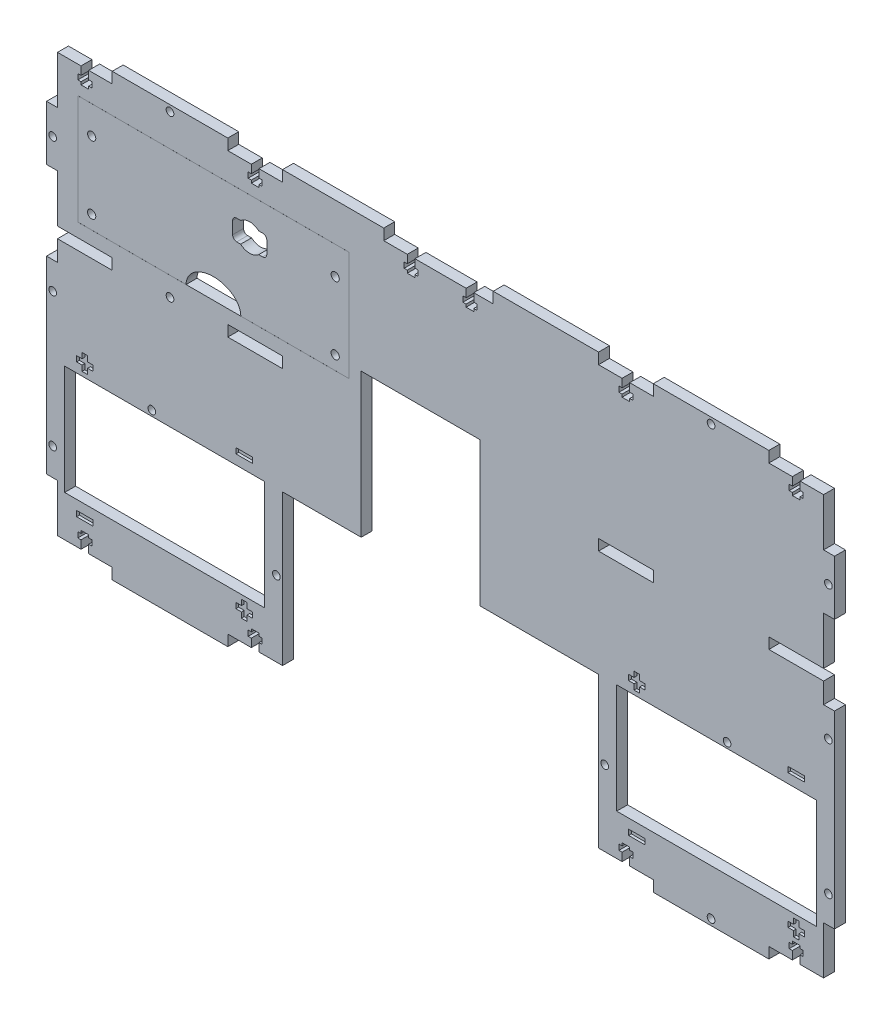
SolidWorks part; units mm, degrees
ref_plane "Спереди" through (0, 0, 0) normal (0, 0, 1) x (1, 0, 0)
ref_plane "Сверху" through (0, 0, 0) normal (0, 1, 0) x (1, 0, 0)
ref_plane "Справа" through (0, 0, 0) normal (1, 0, 0) x (0, 0, -1)
sketch "Эскиз1" plane through (0, 0, 0) normal (0, 0, 1) x (1, 0, 0)
  line L1 (-144, -80.5) -> (144, -80.5)
  line L2 (-144, -80.5) -> (-144, 80.5)
  line L3 (-144, 80.5) -> (144, 80.5)
  line L4 (144, -80.5) -> (144, 80.5)
  line L5 (-144, -80.5) -> (144, 80.5) construction
  line L6 (-144, 80.5) -> (144, -80.5) construction
  line L14 (144, 59) -> (144, 80.5) construction
  line L15 (144, 80.5) -> (140, 80.5) construction
  line L16 (140, 80.5) -> (140, 59) construction
  line L17 (140, 59) -> (144, 59) construction
  line L18 (140, 80.5) -> (120, 80.5) construction
  line L19 (120, 80.5) -> (120, 76.5) construction
  line L20 (120, 76.5) -> (140, 76.5) construction
  line L21 (140, 76.5) -> (140, 80.5) construction
  line L22 (77.75, 80.5) -> (57.75, 80.5) construction
  line L23 (57.75, 80.5) -> (57.75, 76.5) construction
  line L24 (57.75, 76.5) -> (77.75, 76.5) construction
  line L25 (77.75, 76.5) -> (77.75, 80.5) construction
  line L26 (19.25, 80.5) -> (-20.75, 80.5) construction
  line L27 (-20.75, 80.5) -> (-20.75, 76.5) construction
  line L28 (-20.75, 76.5) -> (19.25, 76.5) construction
  line L29 (19.25, 76.5) -> (19.25, 80.5) construction
  line L30 (-57.75, 80.5) -> (-77.75, 80.5) construction
  line L31 (-77.75, 80.5) -> (-77.75, 76.5) construction
  line L32 (-77.75, 76.5) -> (-57.75, 76.5) construction
  line L33 (-57.75, 76.5) -> (-57.75, 80.5) construction
  line L34 (-120, 80.5) -> (-140, 80.5) construction
  line L35 (-140, 80.5) -> (-140, 76.5) construction
  line L36 (-140, 76.5) -> (-120, 76.5) construction
  line L37 (-120, 76.5) -> (-120, 80.5) construction
  line L38 (-140, 59) -> (-140, 80.5) construction
  line L39 (-140, 80.5) -> (-144, 80.5) construction
  line L40 (-144, 80.5) -> (-144, 59) construction
  line L41 (-144, 59) -> (-140, 59) construction
  line L42 (-77.75, 17.5) -> (-57.75, 17.5) construction
  line L43 (-57.75, 17.5) -> (-57.75, 21.5) construction
  line L44 (-57.75, 21.5) -> (-77.75, 21.5) construction
  line L45 (-77.75, 21.5) -> (-77.75, 17.5) construction
  line L46 (-140, 17.5) -> (-120, 17.5) construction
  line L47 (-120, 17.5) -> (-120, 21.5) construction
  line L48 (-120, 21.5) -> (-140, 21.5) construction
  line L49 (-140, 21.5) -> (-140, 17.5) construction
  line L50 (-140, 10) -> (-140, 39) construction
  line L51 (-140, 39) -> (-144, 39) construction
  line L52 (-144, 39) -> (-144, 10) construction
  line L53 (-144, 10) -> (-140, 10) construction
  line L54 (57.75, 17.5) -> (77.75, 17.5) construction
  line L55 (77.75, 17.5) -> (77.75, 21.5) construction
  line L56 (77.75, 21.5) -> (57.75, 21.5) construction
  line L57 (57.75, 21.5) -> (57.75, 17.5) construction
  line L58 (120, 17.5) -> (140, 17.5) construction
  line L59 (140, 17.5) -> (140, 21.5) construction
  line L60 (140, 21.5) -> (120, 21.5) construction
  line L61 (120, 21.5) -> (120, 17.5) construction
  line L62 (144, 10) -> (144, 39) construction
  line L63 (144, 39) -> (140, 39) construction
  line L64 (140, 39) -> (140, 10) construction
  line L65 (140, 10) -> (144, 10) construction
  line L66 (144, -80.5) -> (144, -59) construction
  line L67 (144, -59) -> (140, -59) construction
  line L68 (140, -59) -> (140, -80.5) construction
  line L69 (140, -80.5) -> (144, -80.5) construction
  line L70 (144, -80.5) -> (144, -59) construction
  line L71 (144, -59) -> (140, -59) construction
  line L72 (140, -59) -> (140, -80.5) construction
  line L73 (140, -80.5) -> (144, -80.5) construction
  line L82 (140, -76.5) -> (120, -76.5) construction
  line L83 (120, -76.5) -> (120, -80.5) construction
  line L84 (120, -80.5) -> (140, -80.5) construction
  line L85 (140, -80.5) -> (140, -76.5) construction
  line L86 (77.75, -76.5) -> (57.75, -76.5) construction
  line L87 (57.75, -76.5) -> (57.75, -80.5) construction
  line L88 (57.75, -80.5) -> (77.75, -80.5) construction
  line L89 (77.75, -80.5) -> (77.75, -76.5) construction
  line L90 (-140, -80.5) -> (-140, -59) construction
  line L91 (-140, -59) -> (-144, -59) construction
  line L92 (-144, -59) -> (-144, -80.5) construction
  line L93 (-144, -80.5) -> (-140, -80.5) construction
  line L94 (-140, -80.5) -> (-140, -59) construction
  line L95 (-140, -59) -> (-144, -59) construction
  line L96 (-144, -59) -> (-144, -80.5) construction
  line L97 (-144, -80.5) -> (-140, -80.5) construction
  line L98 (-120, -76.5) -> (-140, -76.5) construction
  line L99 (-140, -76.5) -> (-140, -80.5) construction
  line L100 (-140, -80.5) -> (-120, -80.5) construction
  line L101 (-120, -80.5) -> (-120, -76.5) construction
  line L102 (-57.75, -76.5) -> (-77.75, -76.5) construction
  line L103 (-77.75, -76.5) -> (-77.75, -80.5) construction
  line L104 (-77.75, -80.5) -> (-57.75, -80.5) construction
  line L105 (-57.75, -80.5) -> (-57.75, -76.5) construction
  line L107 (13.3, 73.5) -> (8.2, 71.5) construction
  line L116 (144, 59) -> (144, 80.5)
  line L117 (144, 80.5) -> (140, 80.5)
  line L118 (140, 80.5) -> (140, 59)
  line L119 (140, 59) -> (144, 59)
  line L120 (140, 80.5) -> (120, 80.5)
  line L121 (120, 80.5) -> (120, 76.5)
  line L122 (120, 76.5) -> (140, 76.5)
  line L123 (140, 76.5) -> (140, 80.5)
  line L124 (77.75, 80.5) -> (57.75, 80.5) construction
  line L125 (57.75, 80.5) -> (57.75, 76.5)
  line L126 (57.75, 76.5) -> (77.75, 76.5)
  line L127 (77.75, 76.5) -> (77.75, 80.5)
  line L128 (19.25, 80.5) -> (-20.75, 80.5) construction
  line L129 (-20.75, 80.5) -> (-20.75, 76.5)
  line L130 (-20.75, 76.5) -> (19.25, 76.5)
  line L131 (19.25, 76.5) -> (19.25, 80.5)
  line L132 (-57.75, 80.5) -> (-77.75, 80.5) construction
  line L133 (-77.75, 80.5) -> (-77.75, 76.5)
  line L134 (-77.75, 76.5) -> (-57.75, 76.5)
  line L135 (-57.75, 76.5) -> (-57.75, 80.5)
  line L136 (-120, 80.5) -> (-140, 80.5) construction
  line L137 (-140, 80.5) -> (-140, 76.5)
  line L138 (-140, 76.5) -> (-120, 76.5)
  line L139 (-120, 76.5) -> (-120, 80.5)
  line L140 (-140, 59) -> (-140, 80.5)
  line L141 (-140, 80.5) -> (-144, 80.5)
  line L142 (-144, 80.5) -> (-144, 59)
  line L143 (-144, 59) -> (-140, 59)
  line L144 (-77.75, 17.5) -> (-57.75, 17.5)
  line L145 (-57.75, 17.5) -> (-57.75, 21.5)
  line L146 (-57.75, 21.5) -> (-77.75, 21.5)
  line L147 (-77.75, 21.5) -> (-77.75, 17.5)
  line L148 (-140, 17.5) -> (-120, 17.5)
  line L149 (-120, 17.5) -> (-120, 21.5)
  line L150 (-120, 21.5) -> (-140, 21.5)
  line L151 (-140, 21.5) -> (-140, 17.5)
  line L152 (-140, 10) -> (-140, 39)
  line L153 (-140, 39) -> (-144, 39)
  line L154 (-144, 39) -> (-144, 10)
  line L155 (-144, 10) -> (-140, 10)
  line L156 (57.75, 17.5) -> (77.75, 17.5)
  line L157 (77.75, 17.5) -> (77.75, 21.5)
  line L158 (77.75, 21.5) -> (57.75, 21.5)
  line L159 (57.75, 21.5) -> (57.75, 17.5)
  line L160 (120, 17.5) -> (140, 17.5)
  line L161 (140, 17.5) -> (140, 21.5)
  line L162 (140, 21.5) -> (120, 21.5)
  line L163 (120, 21.5) -> (120, 17.5)
  line L164 (144, 10) -> (144, 39)
  line L165 (144, 39) -> (140, 39)
  line L166 (140, 39) -> (140, 10)
  line L167 (140, 10) -> (144, 10)
  line L168 (144, -80.5) -> (144, -59)
  line L169 (144, -59) -> (140, -59)
  line L170 (140, -59) -> (140, -80.5)
  line L171 (140, -80.5) -> (144, -80.5)
  line L172 (144, -80.5) -> (144, -59)
  line L173 (144, -59) -> (140, -59)
  line L174 (140, -59) -> (140, -80.5)
  line L175 (140, -80.5) -> (144, -80.5)
  line L184 (140, -76.5) -> (120, -76.5)
  line L185 (120, -76.5) -> (120, -80.5)
  line L186 (120, -80.5) -> (140, -80.5)
  line L187 (140, -80.5) -> (140, -76.5)
  line L188 (77.75, -76.5) -> (57.75, -76.5)
  line L189 (57.75, -76.5) -> (57.75, -80.5)
  line L190 (57.75, -80.5) -> (77.75, -80.5)
  line L191 (77.75, -80.5) -> (77.75, -76.5)
  line L192 (-140, -80.5) -> (-140, -59)
  line L193 (-140, -59) -> (-144, -59)
  line L194 (-144, -59) -> (-144, -80.5)
  line L195 (-144, -80.5) -> (-140, -80.5)
  line L196 (-140, -80.5) -> (-140, -59)
  line L197 (-140, -59) -> (-144, -59)
  line L198 (-144, -59) -> (-144, -80.5)
  line L199 (-144, -80.5) -> (-140, -80.5)
  line L200 (-120, -76.5) -> (-140, -76.5)
  line L201 (-140, -76.5) -> (-140, -80.5)
  line L202 (-140, -80.5) -> (-120, -80.5)
  line L203 (-120, -80.5) -> (-120, -76.5)
  line L204 (-57.75, -76.5) -> (-77.75, -76.5)
  line L205 (-77.75, -76.5) -> (-77.75, -80.5)
  line L206 (-77.75, -80.5) -> (-57.75, -80.5)
  line L207 (-57.75, -80.5) -> (-57.75, -76.5)
  line L209 (-131.4, 76.5) -> (-128.6, 76.5)
  line L210 (-131.4, 76.5) -> (-131.4, 70.5)
  line L211 (-57.75, -80.5) -> (57.75, -80.5)
  line L212 (-57.75, -80.5) -> (-57.75, -21.5)
  line L213 (-57.75, -21.5) -> (57.75, -21.5)
  line L214 (57.75, -80.5) -> (57.75, -21.5)
  line L215 (-29, -21.5) -> (14.5, -21.5)
  line L216 (-29, -21.5) -> (-29, 31.1)
  line L217 (-29, 31.1) -> (14.5, 31.1)
  line L218 (14.5, -21.5) -> (14.5, 31.1)
  line L219 (-100.375, 76.5) -> (-97.375, 76.5) construction
  line L220 (-140, 50.4) -> (-140, 47.6) construction
  line L221 (-97.375, 21.5) -> (-97.375, 17.5) construction
  line L222 (-140, -50.4) -> (-140, -47.6) construction
  line L223 (-61.75, -50.5) -> (-61.75, -47.5) construction
  line L224 (-107, -21.5) -> (-104, -21.5) construction
  line L225 (-107, -21.5) -> (-107, -17.5) construction
  line L226 (0, -55) -> (0, 55) construction
  line L227 (69.15, -76.5) -> (66.35, -76.5) construction
  line L228 (131.4, -76.5) -> (128.6, -76.5) construction
  line L229 (-66.35, -76.5) -> (-69.15, -76.5) construction
  line L230 (-128.6, -76.5) -> (-131.4, -76.5) construction
  line L231 (131.4, 80.5) -> (128.6, 80.5) construction
  line L232 (69.15, 80.5) -> (66.35, 80.5) construction
  line L233 (10.65, 80.5) -> (7.85, 80.5) construction
  line L234 (-9.35, 80.5) -> (-12.15, 80.5) construction
  line L235 (-66.35, 80.5) -> (-69.15, 80.5) construction
  line L236 (-128.6, 80.5) -> (-131.4, 80.5) construction
  line L237 (69.15, -76.5) -> (66.35, -76.5)
  line L238 (131.4, -76.5) -> (128.6, -76.5)
  line L239 (-66.35, -76.5) -> (-69.15, -76.5)
  line L240 (-128.6, -76.5) -> (-131.4, -76.5)
  line L241 (131.4, 80.5) -> (128.6, 80.5)
  line L242 (69.15, 80.5) -> (66.35, 80.5)
  line L243 (10.65, 80.5) -> (7.85, 80.5)
  line L244 (-9.35, 80.5) -> (-12.15, 80.5)
  line L245 (-66.35, 80.5) -> (-69.15, 80.5)
  line L246 (-128.6, 80.5) -> (-131.4, 80.5)
  line L247 (-131.4, 70.5) -> (-128.6, 70.5)
  line L248 (-128.6, 76.5) -> (-128.6, 70.5)
  line L249 (-132.55, 71.5) -> (-127.45, 71.5)
  line L250 (-132.55, 71.5) -> (-132.55, 73.5)
  line L251 (-132.55, 73.5) -> (-127.45, 73.5)
  line L252 (-127.45, 71.5) -> (-127.45, 73.5)
  line L253 (-132.55, 71.5) -> (-127.45, 73.5) construction
  line L254 (-132.55, 73.5) -> (-127.45, 71.5) construction
  line L255 (-69.15, 70.5) -> (-66.35, 70.5)
  line L256 (-69.15, 70.5) -> (-69.15, 76.5)
  line L257 (-69.15, 76.5) -> (-66.35, 76.5)
  line L258 (-66.35, 70.5) -> (-66.35, 76.5)
  line L259 (-69.15, 70.5) -> (-66.35, 76.5) construction
  line L260 (-69.15, 76.5) -> (-66.35, 70.5) construction
  line L261 (-70.3, 71.5) -> (-65.2, 71.5)
  line L262 (-70.3, 71.5) -> (-70.3, 73.5)
  line L263 (-70.3, 73.5) -> (-65.2, 73.5)
  line L264 (-65.2, 71.5) -> (-65.2, 73.5)
  line L265 (-70.3, 71.5) -> (-65.2, 73.5) construction
  line L266 (-70.3, 73.5) -> (-65.2, 71.5) construction
  line L267 (-12.15, 70.5) -> (-9.35, 70.5)
  line L268 (-12.15, 70.5) -> (-12.15, 76.5)
  line L269 (-12.15, 76.5) -> (-9.35, 76.5)
  line L270 (-9.35, 70.5) -> (-9.35, 76.5)
  line L271 (-12.15, 70.5) -> (-9.35, 76.5) construction
  line L272 (-12.15, 76.5) -> (-9.35, 70.5) construction
  line L273 (-13.3, 71.5) -> (-8.2, 71.5)
  line L274 (-13.3, 71.5) -> (-13.3, 73.5)
  line L275 (-13.3, 73.5) -> (-8.2, 73.5)
  line L276 (-8.2, 71.5) -> (-8.2, 73.5)
  line L277 (-13.3, 71.5) -> (-8.2, 73.5) construction
  line L278 (-13.3, 73.5) -> (-8.2, 71.5) construction
  line L279 (13.3, 71.5) -> (8.2, 73.5) construction
  line L280 (12.15, 76.5) -> (9.35, 70.5) construction
  line L281 (12.15, 70.5) -> (9.35, 76.5) construction
  line L282 (8.2, 71.5) -> (8.2, 73.5)
  line L283 (13.3, 73.5) -> (8.2, 73.5)
  line L284 (13.3, 71.5) -> (13.3, 73.5)
  line L285 (13.3, 71.5) -> (8.2, 71.5)
  line L286 (9.35, 70.5) -> (9.35, 76.5)
  line L287 (12.15, 76.5) -> (9.35, 76.5)
  line L288 (12.15, 70.5) -> (12.15, 76.5)
  line L289 (12.15, 70.5) -> (9.35, 70.5)
  line L290 (70.3, 73.5) -> (65.2, 71.5) construction
  line L291 (70.3, 71.5) -> (65.2, 73.5) construction
  line L292 (69.15, 76.5) -> (66.35, 70.5) construction
  line L293 (69.15, 70.5) -> (66.35, 76.5) construction
  line L294 (65.2, 71.5) -> (65.2, 73.5)
  line L295 (70.3, 73.5) -> (65.2, 73.5)
  line L296 (70.3, 71.5) -> (70.3, 73.5)
  line L297 (70.3, 71.5) -> (65.2, 71.5)
  line L298 (66.35, 70.5) -> (66.35, 76.5)
  line L299 (69.15, 76.5) -> (66.35, 76.5)
  line L300 (69.15, 70.5) -> (69.15, 76.5)
  line L301 (69.15, 70.5) -> (66.35, 70.5)
  line L302 (132.55, 73.5) -> (127.45, 71.5) construction
  line L303 (132.55, 71.5) -> (127.45, 73.5) construction
  line L304 (127.45, 71.5) -> (127.45, 73.5)
  line L305 (132.55, 73.5) -> (127.45, 73.5)
  line L306 (132.55, 71.5) -> (132.55, 73.5)
  line L307 (132.55, 71.5) -> (127.45, 71.5)
  line L308 (128.6, 76.5) -> (128.6, 70.5)
  line L309 (131.4, 70.5) -> (128.6, 70.5)
  line L310 (131.4, 76.5) -> (131.4, 70.5)
  line L311 (131.4, 76.5) -> (128.6, 76.5)
  line L312 (55, 0) -> (-55, 0) construction
  line L313 (132.55, -71.5) -> (127.45, -73.5) construction
  line L314 (132.55, -73.5) -> (127.45, -71.5) construction
  line L315 (131.4, -76.5) -> (128.6, -76.5)
  line L316 (131.4, -76.5) -> (131.4, -70.5)
  line L317 (131.4, -70.5) -> (128.6, -70.5)
  line L318 (128.6, -76.5) -> (128.6, -70.5)
  line L319 (132.55, -71.5) -> (127.45, -71.5)
  line L320 (132.55, -71.5) -> (132.55, -73.5)
  line L321 (132.55, -73.5) -> (127.45, -73.5)
  line L322 (127.45, -71.5) -> (127.45, -73.5)
  line L323 (69.15, -70.5) -> (66.35, -76.5) construction
  line L324 (69.15, -76.5) -> (66.35, -70.5) construction
  line L325 (70.3, -71.5) -> (65.2, -73.5) construction
  line L326 (70.3, -73.5) -> (65.2, -71.5) construction
  line L327 (69.15, -70.5) -> (66.35, -70.5)
  line L328 (69.15, -70.5) -> (69.15, -76.5)
  line L329 (69.15, -76.5) -> (66.35, -76.5)
  line L330 (66.35, -70.5) -> (66.35, -76.5)
  line L331 (70.3, -71.5) -> (65.2, -71.5)
  line L332 (70.3, -71.5) -> (70.3, -73.5)
  line L333 (70.3, -73.5) -> (65.2, -73.5)
  line L334 (65.2, -71.5) -> (65.2, -73.5)
  line L335 (-70.3, -73.5) -> (-65.2, -71.5) construction
  line L336 (-70.3, -71.5) -> (-65.2, -73.5) construction
  line L337 (-69.15, -76.5) -> (-66.35, -70.5) construction
  line L338 (-69.15, -70.5) -> (-66.35, -76.5) construction
  line L339 (-65.2, -71.5) -> (-65.2, -73.5)
  line L340 (-70.3, -73.5) -> (-65.2, -73.5)
  line L341 (-70.3, -71.5) -> (-70.3, -73.5)
  line L342 (-70.3, -71.5) -> (-65.2, -71.5)
  line L343 (-66.35, -70.5) -> (-66.35, -76.5)
  line L344 (-69.15, -76.5) -> (-66.35, -76.5)
  line L345 (-69.15, -70.5) -> (-69.15, -76.5)
  line L346 (-69.15, -70.5) -> (-66.35, -70.5)
  line L347 (-132.55, -73.5) -> (-127.45, -71.5) construction
  line L348 (-132.55, -71.5) -> (-127.45, -73.5) construction
  line L349 (-127.45, -71.5) -> (-127.45, -73.5)
  line L350 (-132.55, -73.5) -> (-127.45, -73.5)
  line L351 (-132.55, -71.5) -> (-132.55, -73.5)
  line L352 (-132.55, -71.5) -> (-127.45, -71.5)
  line L353 (-128.6, -76.5) -> (-128.6, -70.5)
  line L354 (-131.4, -70.5) -> (-128.6, -70.5)
  line L355 (-131.4, -76.5) -> (-131.4, -70.5)
  line L356 (-131.4, -76.5) -> (-128.6, -76.5)
  line L357 (103.25, -17.5) -> (106.25, -17.5) construction
  line L358 (106.25, -21.5) -> (106.25, -17.5) construction
  line L359 (-140, -65.5479) -> (-61.75, -65.5479) construction
  line L360 (-137.375, -61.5) -> (-64.375, -61.5)
  line L361 (-137.375, -61.5) -> (-137.375, -21.5)
  line L362 (-137.375, -21.5) -> (-64.375, -21.5)
  line L363 (-64.375, -61.5) -> (-64.375, -21.5)
  line L364 (-137.375, -61.5) -> (-64.375, -21.5) construction
  line L365 (-137.375, -21.5) -> (-64.375, -61.5) construction
  line L367 (137.375, -21.5) -> (64.375, -61.5) construction
  line L368 (137.375, -61.5) -> (64.375, -21.5) construction
  line L369 (64.375, -61.5) -> (64.375, -21.5)
  line L370 (137.375, -21.5) -> (64.375, -21.5)
  line L371 (137.375, -61.5) -> (137.375, -21.5)
  line L372 (137.375, -61.5) -> (64.375, -61.5)
  circle A0 centre (-98.875, 78.25) radius 1.4
  circle A1 centre (-98.875, 19.5) radius 1.4
  circle A2 centre (-105.5, -19.5) radius 1.4
  circle A3 centre (-60, -49) radius 1.4
  circle A4 centre (-141.75, -49) radius 1.4
  circle A5 centre (-141.75, 49) radius 1.4
  circle A6 centre (-141.75, 0) radius 1.4
  circle A7 centre (98.875, 78.25) radius 1.4
  circle A8 centre (98.875, 19.5) radius 1.4
  circle A9 centre (104.75, -19.5) radius 1.4
  circle A10 centre (60, -49) radius 1.4
  circle A11 centre (141.75, -49) radius 1.4
  circle A12 centre (141.75, 0) radius 1.4
  circle A13 centre (141.75, 49) radius 1.4
  circle A14 centre (98.875, -78.25) radius 1.4
  circle A15 centre (-38.5, 31.5) radius 1.5
  circle A16 centre (-127.5, 31.5) radius 1.5
  circle A17 centre (-38.5, 56.25) radius 1.5
  circle A18 centre (-127.5, 56.25) radius 1.5
  point P0 (0, 0)
  point P15 (100.875, -41.5)
  point P48 (-100.875, -41.5)
  point P50 (-130, 80.5)
  point P56 (-98.875, 76.5)
  point P58 (-67.75, 73.5)
  point P64 (-140, 49)
  point P72 (-97.375, 19.5)
  point P76 (-130, 72.5)
  point P82 (-140, -49)
  point P93 (-61.75, -49)
  point P101 (-105.5, -21.5)
  point P109 (-107, -19.5)
  point P194 (-10.75, 73.5)
  point P196 (-67.75, 80.5)
  point P197 (-67.75, 72.5)
  point P215 (-10.75, 72.5)
  point P227 (10.75, 72.5)
  point P228 (10.75, 73.5)
  point P237 (67.75, 72.5)
  point P238 (67.75, 73.5)
  point P247 (130, 72.5)
  point P258 (130, -72.5)
  point P267 (67.75, -73.5)
  point P268 (67.75, -72.5)
  point P277 (-67.75, -72.5)
  point P278 (-67.75, -73.5)
  point P287 (-130, -72.5)
  point P294 (104.75, -17.5)
  point P298 (106.25, -19.5)
  point P302 (-100.875, -65.5479)
  dimension "D6" = 2.8
  dimension "D20" = 3
  dimension "D1" = 288
  dimension "D2" = 161
  dimension "D3" = 52.6
  dimension "D4" = 43.5
  dimension "D5" = 29
  dimension "D7" = 2.25
  dimension "D8" = 2.25
  dimension "D9" = 2.25
  dimension "D10" = 6
  dimension "D11" = 5.1
  dimension "D12" = 2
  dimension "D13" = 3
  dimension "D14" = 3
  dimension "D15" = 3
  dimension "D16" = 2.25
  dimension "D17" = 4
  dimension "D18" = 73
  dimension "D19" = 40
extrude "Бобышка-Вытянуть1" add sketch "Эскиз1" along normal blind 4 contours L1 L4 L3 L2 | A8 region at (-140.7005, -24.5, 0) region at (98.875, 19.5, 0)
sketch "Эскиз2" plane through (0, 0, 4) normal (0, 0, 1) x (1, 0, 0)
  line L0 (-127.5, 31.5) -> (-38.5, 31.5) construction
  line L1 (-132.5, 66.5) -> (-33.5, 66.5)
  line L2 (-132.5, 66.5) -> (-132.5, 26.5)
  line L3 (-132.5, 26.5) -> (-33.5, 26.5)
  line L4 (-33.5, 66.5) -> (-33.5, 26.5)
  line L5 (-132.5, 66.5) -> (-33.5, 26.5) construction
  line L6 (-132.5, 26.5) -> (-33.5, 66.5) construction
  line L7 (-77.75, 76.5) -> (-69.15, 76.5) construction
  line L10 (-120, 21.5) -> (-140, 21.5) construction
  point P0 (-83, 46.5)
  point P10 (-83, 31.5)
  dimension "D1" = 10
  dimension "D2" = 5
  dimension "D3" = 5
extrude "Вырез-Вытянуть-Тонкостенный1" cut sketch "Эскиз2" against normal through all thin thin type one direction wall 0.01
sketch "Эскиз3" plane through (0, 0, 4) normal (0, 0, 1) x (1, 0, 0)
  line L0 (131.4, -70.5) -> (128.6, -70.5) construction
  line L1 (127, -67) -> (133, -67)
  line L2 (127, -67) -> (127, -65)
  line L3 (127, -65) -> (133, -65)
  line L4 (133, -67) -> (133, -65)
  line L5 (127, -67) -> (133, -65) construction
  line L6 (127, -65) -> (133, -67) construction
  line L7 (129, -63) -> (131, -63)
  line L8 (129, -63) -> (129, -69)
  line L9 (129, -69) -> (131, -69)
  line L10 (131, -63) -> (131, -69)
  line L11 (129, -63) -> (131, -69) construction
  line L12 (129, -69) -> (131, -63) construction
  line L13 (130, -61.5) -> (130, -70.5) construction
  line L14 (137.375, -61.5) -> (64.375, -61.5) construction
  line L15 (64.375, -41.5) -> (137.375, -41.5) construction
  line L16 (64.375, -61.5) -> (64.375, -21.5) construction
  line L17 (137.375, -61.5) -> (137.375, -21.5) construction
  line L18 (100.875, -21.5) -> (100.875, -61.5) construction
  line L19 (137.375, -21.5) -> (64.375, -21.5) construction
  line L20 (71.75, -61.5) -> (71.75, -70.5) construction
  line L21 (72.75, -69) -> (70.75, -63) construction
  line L22 (72.75, -63) -> (70.75, -69) construction
  line L23 (74.75, -65) -> (68.75, -67) construction
  line L24 (74.75, -67) -> (68.75, -65) construction
  line L25 (70.75, -63) -> (70.75, -69)
  line L26 (72.75, -69) -> (70.75, -69)
  line L27 (72.75, -63) -> (72.75, -69)
  line L28 (72.75, -63) -> (70.75, -63)
  line L29 (68.75, -67) -> (68.75, -65)
  line L30 (74.75, -65) -> (68.75, -65)
  line L31 (74.75, -67) -> (74.75, -65)
  line L32 (74.75, -67) -> (68.75, -67)
  line L33 (74.75, -16) -> (68.75, -18) construction
  line L34 (74.75, -18) -> (68.75, -16) construction
  line L35 (72.75, -20) -> (70.75, -14) construction
  line L36 (72.75, -14) -> (70.75, -20) construction
  line L37 (71.75, -21.5) -> (71.75, -12.5) construction
  line L38 (130, -21.5) -> (130, -12.5) construction
  line L39 (129, -14) -> (131, -20) construction
  line L40 (129, -20) -> (131, -14) construction
  line L41 (127, -18) -> (133, -16) construction
  line L42 (127, -16) -> (133, -18) construction
  line L43 (74.75, -16) -> (68.75, -16)
  line L44 (74.75, -16) -> (74.75, -18)
  line L45 (74.75, -18) -> (68.75, -18)
  line L46 (68.75, -16) -> (68.75, -18)
  line L47 (72.75, -20) -> (70.75, -20)
  line L48 (72.75, -20) -> (72.75, -14)
  line L49 (72.75, -14) -> (70.75, -14)
  line L50 (70.75, -20) -> (70.75, -14)
  line L51 (131, -20) -> (131, -14)
  line L52 (129, -14) -> (131, -14)
  line L53 (129, -20) -> (129, -14)
  line L54 (129, -20) -> (131, -20)
  line L55 (133, -16) -> (133, -18)
  line L56 (127, -18) -> (133, -18)
  line L57 (127, -16) -> (127, -18)
  line L58 (127, -16) -> (133, -16)
  line L59 (0, -2.2) -> (0, 2.2) construction
  line L60 (-127, -16) -> (-133, -18) construction
  line L61 (-127, -18) -> (-133, -16) construction
  line L62 (-129, -20) -> (-131, -14) construction
  line L63 (-129, -14) -> (-131, -20) construction
  line L64 (-130, -21.5) -> (-130, -12.5) construction
  line L65 (-71.75, -21.5) -> (-71.75, -12.5) construction
  line L66 (-72.75, -14) -> (-70.75, -20) construction
  line L67 (-72.75, -20) -> (-70.75, -14) construction
  line L68 (-74.75, -18) -> (-68.75, -16) construction
  line L69 (-74.75, -16) -> (-68.75, -18) construction
  line L70 (-74.75, -67) -> (-68.75, -65) construction
  line L71 (-74.75, -65) -> (-68.75, -67) construction
  line L72 (-72.75, -63) -> (-70.75, -69) construction
  line L73 (-72.75, -69) -> (-70.75, -63) construction
  line L74 (-71.75, -61.5) -> (-71.75, -70.5) construction
  line L75 (-100.875, -21.5) -> (-100.875, -61.5) construction
  line L76 (-64.375, -41.5) -> (-137.375, -41.5) construction
  line L77 (-130, -61.5) -> (-130, -70.5) construction
  line L78 (-129, -69) -> (-131, -63) construction
  line L79 (-129, -63) -> (-131, -69) construction
  line L80 (-127, -65) -> (-133, -67) construction
  line L81 (-127, -67) -> (-133, -65) construction
  line L82 (-127, -16) -> (-133, -16)
  line L83 (-127, -16) -> (-127, -18)
  line L84 (-127, -18) -> (-133, -18)
  line L85 (-133, -16) -> (-133, -18)
  line L86 (-129, -20) -> (-131, -20)
  line L87 (-129, -20) -> (-129, -14)
  line L88 (-129, -14) -> (-131, -14)
  line L89 (-131, -20) -> (-131, -14)
  line L90 (-70.75, -20) -> (-70.75, -14)
  line L91 (-72.75, -14) -> (-70.75, -14)
  line L92 (-72.75, -20) -> (-72.75, -14)
  line L93 (-72.75, -20) -> (-70.75, -20)
  line L94 (-68.75, -16) -> (-68.75, -18)
  line L95 (-74.75, -18) -> (-68.75, -18)
  line L96 (-74.75, -16) -> (-74.75, -18)
  line L97 (-74.75, -16) -> (-68.75, -16)
  line L98 (-74.75, -67) -> (-68.75, -67)
  line L99 (-74.75, -67) -> (-74.75, -65)
  line L100 (-74.75, -65) -> (-68.75, -65)
  line L101 (-68.75, -67) -> (-68.75, -65)
  line L102 (-72.75, -63) -> (-70.75, -63)
  line L103 (-72.75, -63) -> (-72.75, -69)
  line L104 (-72.75, -69) -> (-70.75, -69)
  line L105 (-70.75, -63) -> (-70.75, -69)
  line L106 (-131, -63) -> (-131, -69)
  line L107 (-129, -69) -> (-131, -69)
  line L108 (-129, -63) -> (-129, -69)
  line L109 (-129, -63) -> (-131, -63)
  line L110 (-133, -67) -> (-133, -65)
  line L111 (-127, -65) -> (-133, -65)
  line L112 (-127, -67) -> (-127, -65)
  line L113 (-127, -67) -> (-133, -67)
  point P0 (130, -66)
  point P5 (130, -66)
  point P13 (130, -70.5)
  point P37 (71.75, -66)
  point P58 (71.75, -17)
  point P59 (130, -17)
  point P106 (-130, -17)
  point P107 (-71.75, -17)
  point P108 (-71.75, -66)
  point P109 (-130, -66)
  dimension "D1" = 2
  dimension "D2" = 6
extrude "Вырез-Вытянуть1" cut sketch "Эскиз3" against normal blind 1 contours L4 L3 L2 L1 | L7 L10 L9 L8 | L31 L30 L29 L32 | L44 L45 L46 L43 | L49 L50 L47 L48 | L55 L56 L57 L58 | L83 L84 L85 L82 | L88 L89 L86 L87 | L94 L95 L96 L97 | L101 L100 L99 L98 | L102 L105 L104 L103 | L112 L111 L110 L113
sketch "Эскиз4" plane through (0, 0, 4) normal (0, 0, 1) x (1, 0, 0)
  line L0 (-132.5, 26.5) -> (-33.5, 26.5) construction
  line L1 (-93, 26.5) -> (-73, 26.5)
  line L2 (-69.15, 70.5) -> (-66.35, 70.5) construction
  line L3 (-76, 49.25) -> (-63.5, 49.25)
  line L4 (-76, 49.25) -> (-76, 56.75)
  line L5 (-76, 56.75) -> (-63.5, 56.75)
  line L6 (-63.5, 49.25) -> (-63.5, 56.75)
  line L7 (-76, 49.25) -> (-63.5, 56.75) construction
  line L8 (-76, 56.75) -> (-63.5, 49.25) construction
  circle A0 centre (-69.75, 53) radius 5
  ellipse E0 centre (-83, 26.5) end of major axis (-93, 26.5) minor radius 7.5
  point P5 (-83, 26.5)
  point P6 (-69.75, 53)
  point P18 (-67.75, 70.5)
  line M5 (-132.5, 26.5) -> (-33.5, 26.5)
  dimension "D1" = 20
  dimension "D7" = 10
  dimension "D2" = 7.5
  dimension "D3" = 2
  dimension "D4" = 17.5
  dimension "D5" = 7.5
  dimension "D6" = 12.5
extrude "Вырез-Вытянуть2" cut sketch "Эскиз4" against normal through all contours E0 M5 | L5 L6 L3 L4 | A0 region at (-83, 29.6831, 4)
fillet "Скругление1" radius 1.5 4 edges at (-76, 56.75, 2) (-76, 49.25, 2) (-63.5, 49.25, 2) (-63.5, 56.75, 2)
